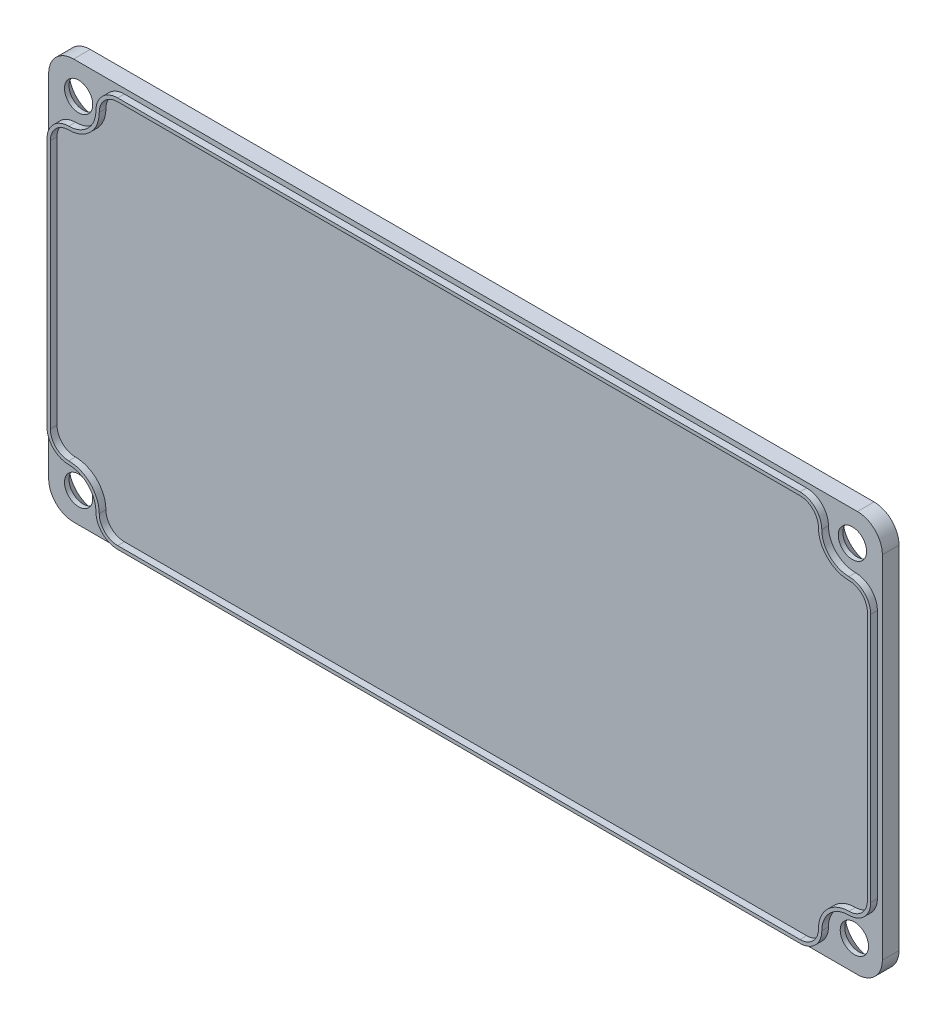
SolidWorks part; units mm, degrees
ref_plane "Plan de face" through (0, 0, 0) normal (0, 0, 1) x (1, 0, 0)
ref_plane "Plan de dessus" through (0, 0, 0) normal (0, 1, 0) x (1, 0, 0)
ref_plane "Plan de droite" through (0, 0, 0) normal (1, 0, 0) x (0, 0, -1)
sketch "Esquisse1" plane through (0, 0, 0) normal (0, 0, 1) x (1, 0, 0)
  line L0 (-50.1, -15) -> (-50.1, 21.1)
  line L1 (-47.1, 24.1) -> (47.1, 24.1)
  line L2 (50.1, 21.1) -> (50.1, -21.1)
  line L3 (47.1, -24.1) -> (-47.1, -24.1)
  line L4 (-50.1, -21.1) -> (-50.1, -15)
  arc A0 (-50.1, 21.1) -> (-47.1, 24.1) centre (-47.1, 21.1) cw
  arc A1 (47.1, 24.1) -> (50.1, 21.1) centre (47.1, 21.1) cw
  arc A2 (50.1, -21.1) -> (47.1, -24.1) centre (47.1, -21.1) cw
  arc A3 (-47.1, -24.1) -> (-50.1, -21.1) centre (-47.1, -21.1) cw
extrude "Boss.-Extru.1" add sketch "Esquisse1" along normal blind 2
sketch "Esquisse2" plane through (0, 0, 0) normal (0, 0, 1) x (1, 0, 0)
  line L0 (-41, 22.5) -> (41, 22.5) construction
  line L1 (48.5, 15) -> (48.5, -15) construction
  line L2 (41, -22.5) -> (-41, -22.5) construction
  line L3 (-48.5, -15) -> (-48.5, 15) construction
  line L4 (-49.7, -15) -> (-49.7, 15) construction
  line L5 (-41, 23.7) -> (41, 23.7) construction
  line L6 (49.7, 15) -> (49.7, -15) construction
  line L7 (41, -23.7) -> (-41, -23.7) construction
  line L8 (41, -23.3) -> (-41, -23.3)
  line L9 (-49.3, -15) -> (-49.3, 15)
  line L10 (-41, 23.3) -> (41, 23.3)
  line L11 (49.3, 15) -> (49.3, -15)
  arc A0 (41, 22.5) -> (42.62, 20.88) centre (41, 20.88) cw construction
  arc A1 (42.62, 20.88) -> (46.88, 16.62) centre (46.88, 20.88) ccw construction
  arc A2 (46.88, 16.62) -> (48.5, 15) centre (46.88, 15) cw construction
  arc A3 (48.5, -15) -> (46.88, -16.62) centre (46.88, -15) cw construction
  arc A4 (46.88, -16.62) -> (42.62, -20.88) centre (46.88, -20.88) ccw construction
  arc A5 (42.62, -20.88) -> (41, -22.5) centre (41, -20.88) cw construction
  arc A6 (-41, -22.5) -> (-42.62, -20.88) centre (-41, -20.88) cw construction
  arc A7 (-42.62, -20.88) -> (-46.88, -16.62) centre (-46.88, -20.88) ccw construction
  arc A8 (-46.88, -16.62) -> (-48.5, -15) centre (-46.88, -15) cw construction
  arc A9 (-48.5, 15) -> (-46.88, 16.62) centre (-46.88, 15) cw construction
  arc A10 (-46.88, 16.62) -> (-42.62, 20.88) centre (-46.88, 20.88) ccw construction
  arc A11 (-42.62, 20.88) -> (-41, 22.5) centre (-41, 20.88) cw construction
  arc A12 (-49.7, 15) -> (-46.88, 17.82) centre (-46.88, 15) cw construction
  arc A13 (-46.88, 17.82) -> (-43.82, 20.88) centre (-46.88, 20.88) ccw construction
  arc A14 (-43.82, 20.88) -> (-41, 23.7) centre (-41, 20.88) cw construction
  arc A15 (41, 23.7) -> (43.82, 20.88) centre (41, 20.88) cw construction
  arc A16 (43.82, 20.88) -> (46.88, 17.82) centre (46.88, 20.88) ccw construction
  arc A17 (46.88, 17.82) -> (49.7, 15) centre (46.88, 15) cw construction
  arc A18 (49.7, -15) -> (46.88, -17.82) centre (46.88, -15) cw construction
  arc A19 (46.88, -17.82) -> (43.82, -20.88) centre (46.88, -20.88) ccw construction
  arc A20 (43.82, -20.88) -> (41, -23.7) centre (41, -20.88) cw construction
  arc A21 (-41, -23.7) -> (-43.82, -20.88) centre (-41, -20.88) cw construction
  arc A22 (-43.82, -20.88) -> (-46.88, -17.82) centre (-46.88, -20.88) ccw construction
  arc A23 (-46.88, -17.82) -> (-49.7, -15) centre (-46.88, -15) cw construction
  arc A24 (-41, -23.3) -> (-43.42, -20.88) centre (-41, -20.88) cw
  arc A25 (-43.42, -20.88) -> (-46.88, -17.42) centre (-46.88, -20.88) ccw
  arc A26 (-46.88, -17.42) -> (-49.3, -15) centre (-46.88, -15) cw
  arc A27 (-49.3, 15) -> (-46.88, 17.42) centre (-46.88, 15) cw
  arc A28 (-46.88, 17.42) -> (-43.42, 20.88) centre (-46.88, 20.88) ccw
  arc A29 (-43.42, 20.88) -> (-41, 23.3) centre (-41, 20.88) cw
  arc A30 (41, 23.3) -> (43.42, 20.88) centre (41, 20.88) cw
  arc A31 (43.42, 20.88) -> (46.88, 17.42) centre (46.88, 20.88) ccw
  arc A32 (46.88, 17.42) -> (49.3, 15) centre (46.88, 15) cw
  arc A33 (49.3, -15) -> (46.88, -17.42) centre (46.88, -15) cw
  arc A34 (46.88, -17.42) -> (43.42, -20.88) centre (46.88, -20.88) ccw
  arc A35 (43.42, -20.88) -> (41, -23.3) centre (41, -20.88) cw
  dimension "D1" = 1.2
  dimension "D2" = 0.8
extrude "Extru.-Mince1" add sketch "Esquisse2" along normal blind 2.8 thin thin type mid plane wall 0.4
hole_wizard "Fraisage pour vis à tête fraisée M31" positions "Esquisse3" profile "Esquisse4" countersink size "M3" standard "Ansi Metric" end condition up to next
sketch "Esquisse3" plane through (0, 0, 0) normal (0, 0, -1) x (-1, 0, 0)
  point P0 (-46.5, 20.5)
  point P3 (46.5, 20.5)
  point P6 (46.5, -20.5)
  point P9 (-46.7338, -20.5)
sketch "Esquisse4" plane through (46.5, 20.5, 0) normal (1, 0, 0) x (0, 1, 0)
  line L0 (0, 0) -> (0, 2)
  line L1 (0, 2) -> (1.7, 2)
  line L2 (1.7, 2) -> (1.7, 1.45)
  line L3 (1.7, 1.45) -> (3.15, 0)
  line L5 (3.15, 0) -> (0, 0)
  line L6 (-1.7, 1.45) -> (-3.15, 0) construction
  line L11 (0, -6.35) -> (0, 107.95) construction
  dimension "Diamètre du perçage jusqu'au prochain" = 3.4
  dimension "Profondeur du perçage jusqu'au prochain" = 2
  dimension "Diamètre du fraisage entrant" = 6.3
  dimension "Angle du fraisage entrant" = 90
equation "\"hauteur\"=2"
equation "\"D1@Boss.-Extru.1\"=\"hauteur\""
equation "\"D1@Extru.-Mince1\"=\"hauteur\"+0.8"
